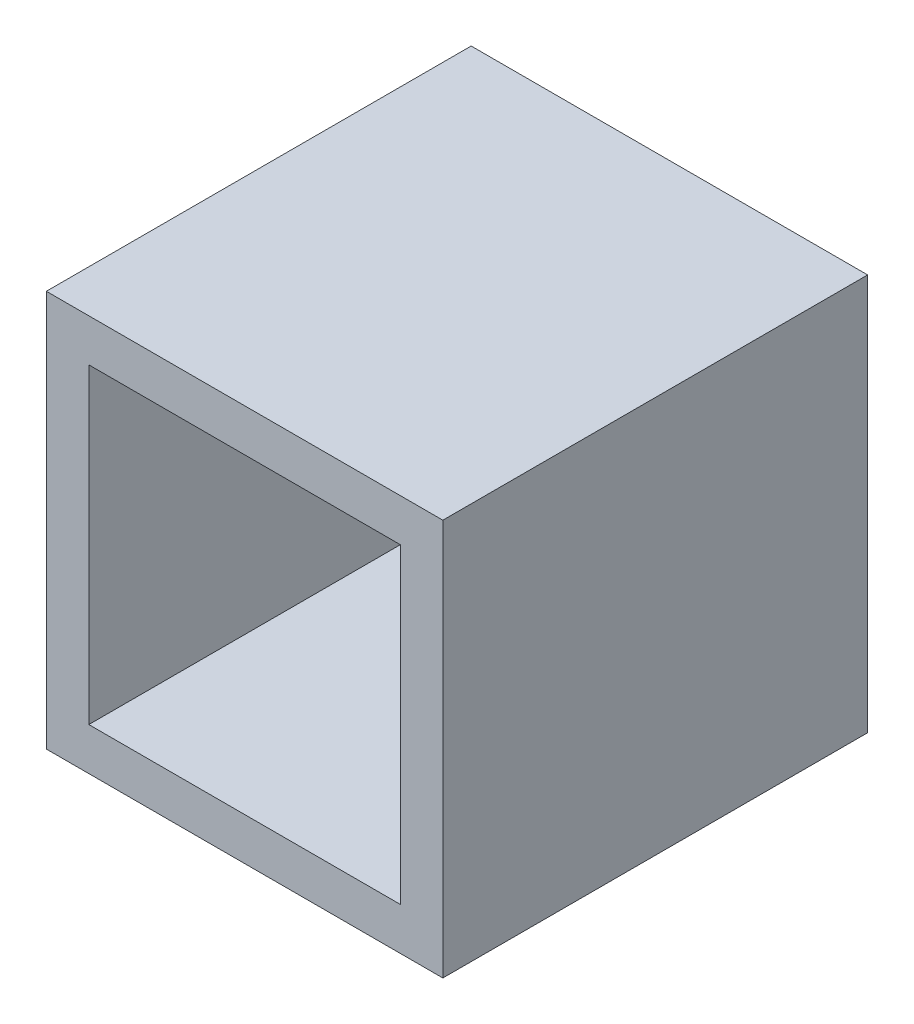
SolidWorks part; units mm, degrees
ref_plane "Front Plane" through (0, 0, 0) normal (0, 0, 1) x (1, 0, 0)
ref_plane "Top Plane" through (0, 0, 0) normal (0, 1, 0) x (1, 0, 0)
ref_plane "Right Plane" through (0, 0, 0) normal (1, 0, 0) x (0, 0, -1)
sketch "Sketch3" plane through (0, 0, 0) normal (0, 0, 1) x (1, 0, 0)
  line L0 (-120.13, 3.5549) -> (124.87, 3.5549) construction
  line L1 (-120.13, 63.5549) -> (124.87, 63.5549)
  line L2 (-120.13, 63.5549) -> (-120.13, -56.4451)
  line L3 (-120.13, -56.4451) -> (124.87, -56.4451)
  line L4 (124.87, 63.5549) -> (124.87, -56.4451)
  line L5 (2.37, 63.5549) -> (2.37, -56.4451) construction
  line L7 (-90.13, 26.0549) -> (-45.13, 26.0549)
  line L8 (-90.13, 26.0549) -> (-90.13, -18.9451)
  line L9 (-90.13, -18.9451) -> (-45.13, -18.9451)
  line L10 (-45.13, 26.0549) -> (-45.13, -18.9451)
  line L11 (-90.13, 26.0549) -> (-45.13, -18.9451) construction
  line L12 (-90.13, -18.9451) -> (-45.13, 26.0549) construction
  line L14 (-4.9072, 3.5549) -> (2.37, -3.7222)
  line L20 (-20.13, -9.4354) -> (13.62, 10.0501) construction
  line L21 (24.87, -9.4354) -> (-8.88, 10.0501) construction
  line L22 (2.37, 29.5357) -> (2.37, 0) construction
  line L24 (-32.63, 38.5549) -> (-102.63, 38.5549)
  line L25 (-32.63, 38.5549) -> (-32.63, -31.4451)
  line L26 (-32.63, -31.4451) -> (-102.63, -31.4451)
  line L27 (-102.63, 38.5549) -> (-102.63, -31.4451)
  line L28 (-32.63, 38.5549) -> (-102.63, -31.4451) construction
  line L29 (-32.63, -31.4451) -> (-102.63, 38.5549) construction
  line L34 (-43.9222, 27.2628) -> (-97.2628, -26.0778) construction
  line L35 (-43.3297, -26.6703) -> (-89.9156, 31.2742) construction
  line L36 (-40.13, 31.0549) -> (-95.13, 31.0549)
  line L37 (-40.13, 31.0549) -> (-40.13, -23.9451)
  line L38 (-40.13, -23.9451) -> (-95.13, -23.9451)
  line L39 (-95.13, 31.0549) -> (-95.13, -23.9451)
  line L40 (-40.13, 31.0549) -> (-95.13, -23.9451) construction
  line L41 (-40.13, -23.9451) -> (-95.13, 31.0549) construction
  point P4 (-67.63, 3.5549)
  point P10 (-67.63, 3.5549)
  point P20 (2.37, 3.5549)
  point P27 (7.7505, -5.3087)
  point P28 (2.37, 3.5549)
  point P32 (-67.63, 3.5549)
  point P38 (-67.63, 3.5549)
  dimension "D1" = 30
  dimension "D4" = 70
  dimension "square2" = 45
  dimension "D5" = 70
  dimension "square" = 45
  dimension "D7" = 55
  dimension "triangle3" = 45
  dimension "triangle2" = 45
  dimension "D8" = 55
  dimension "triangle" = 45
extrude "Boss-Extrude4" add sketch "Sketch3" against normal blind 75 contours L24 L27 L26 L25 L39 L36 L37 L38 region at (-33.62, 3.5549, 0)
